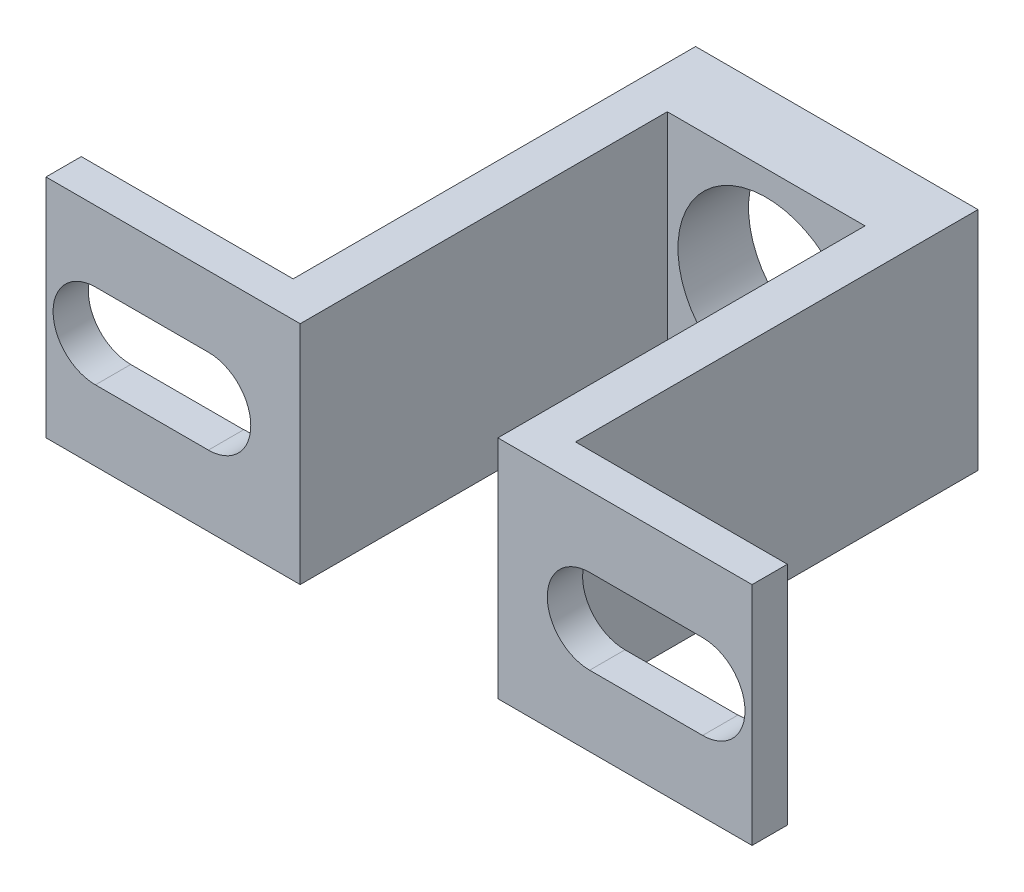
SolidWorks part; units mm, degrees
ref_plane "Front Plane" through (0, 0, 0) normal (0, 0, 1) x (1, 0, 0)
ref_plane "Top Plane" through (0, 0, 0) normal (0, 1, 0) x (1, 0, 0)
ref_plane "Right Plane" through (0, 0, 0) normal (1, 0, 0) x (0, 0, -1)
sketch "Sketch1" plane through (0, 0, 0) normal (0, 0, 1) x (1, 0, 0)
  line L1 (10, -8) -> (-10, -8)
  line L2 (10, -8) -> (10, 8)
  line L3 (10, 8) -> (-10, 8)
  line L4 (-10, -8) -> (-10, 8)
  line L5 (10, -8) -> (-10, 8) construction
  line L6 (10, 8) -> (-10, -8) construction
  circle A0 centre (0, 0) radius 6.25
  dimension "D1" = 12.5
  dimension "D2" = 20
  dimension "D3" = 16
extrude "Boss-Extrude1" add sketch "Sketch1" along normal blind 5
sketch "Sketch2" plane through (0, 0, 5) normal (0, 0, 1) x (1, 0, 0)
  line L0 (-10, -8) -> (10, -8) construction
  line L1 (-10, 8) -> (-7, 8)
  line L2 (-10, 8) -> (-10, -8)
  line L3 (-10, -8) -> (-7, -8)
  line L4 (-7, 8) -> (-7, -8)
  line L5 (0, -8) -> (0, 8) construction
  line L6 (10, 8) -> (-10, 8) construction
  line L7 (7, 8) -> (7, -8)
  line L8 (10, -8) -> (7, -8)
  line L9 (10, 8) -> (10, -8)
  line L10 (10, 8) -> (7, 8)
  dimension "D1" = 7
extrude "Boss-Extrude2" add sketch "Sketch2" along normal blind 26
sketch "Sketch3" plane through (0, 0, 31) normal (0, 0, 1) x (1, 0, 0)
  line L0 (-7, 8) -> (-10, 8) construction
  line L1 (-7, -8) -> (-25, -8)
  line L2 (-7, -8) -> (-7, 8)
  line L3 (-7, 8) -> (-25, 8)
  line L4 (-25, -8) -> (-25, 8)
  line L5 (-10, 8) -> (-10, -8) construction
  line L6 (0, 8) -> (0, -8) construction
  line L7 (7, 8) -> (-7, 8) construction
  line L8 (-7, -8) -> (7, -8) construction
  line L9 (25, -8) -> (25, 8)
  line L10 (7, 8) -> (25, 8)
  line L11 (7, -8) -> (7, 8)
  line L12 (7, -8) -> (25, -8)
  dimension "D1" = 0
  dimension "D2" = 15
extrude "Boss-Extrude3" add sketch "Sketch3" against normal blind 2.5
sketch "Sketch4" plane through (0, 0, 28.5) normal (0, 0, -1) x (-1, 0, 0)
  line L0 (-25, 0) -> (-10, 0) construction
  line L1 (-25, -8) -> (-25, 8) construction
  line L2 (-10, -8) -> (-10, 8) construction
  line L3 (0, -8) -> (0, 8) construction
  line L4 (10, -8) -> (-10, -8) construction
  line L5 (-10, 8) -> (10, 8) construction
  line L6 (-21.5, 0) -> (-13.5, 0) construction
  line L7 (-21.5, 3) -> (-13.5, 3)
  line L8 (-21.5, -3) -> (-13.5, -3)
  line L9 (25, 0) -> (10, 0) construction
  line L10 (21.5, 0) -> (13.5, 0) construction
  line L11 (21.5, 3) -> (13.5, 3)
  line L12 (21.5, -3) -> (13.5, -3)
  arc A0 (-21.5, 3) -> (-21.5, -3) centre (-21.5, 0) ccw
  arc A1 (-13.5, -3) -> (-13.5, 3) centre (-13.5, 0) ccw
  arc A2 (21.5, 3) -> (21.5, -3) centre (21.5, 0) cw
  arc A3 (13.5, -3) -> (13.5, 3) centre (13.5, 0) cw
  point P14 (-17.5, 0)
  point P23 (17.5, 0)
  dimension "D1" = 3
  dimension "D2" = 8
extrude "Cut-Extrude1" cut sketch "Sketch4" against normal through all
